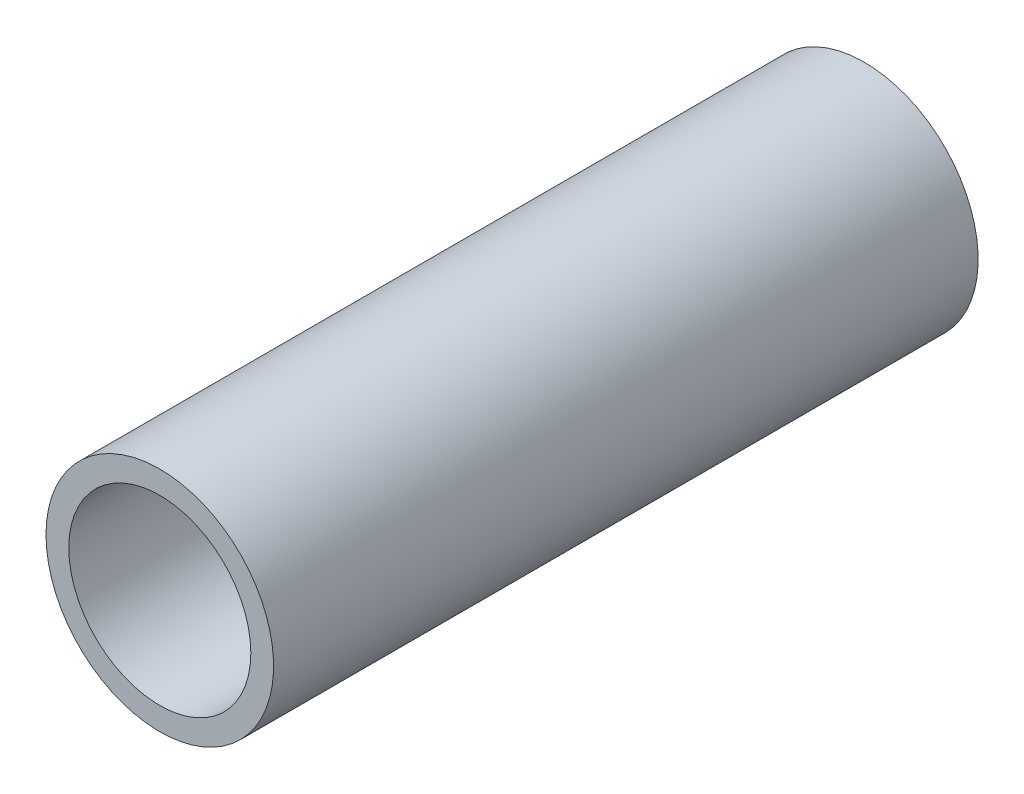
SolidWorks part; units mm, degrees
ref_plane "Front Plane" through (0, 0, 0) normal (0, 0, 1) x (1, 0, 0)
ref_plane "Top Plane" through (0, 0, 0) normal (0, 1, 0) x (1, 0, 0)
ref_plane "Right Plane" through (0, 0, 0) normal (1, 0, 0) x (0, 0, -1)
sketch "Sketch1" plane through (0, 0, 0) normal (0, 0, 1) x (1, 0, 0)
  circle A0 centre (0, 0) radius 1.25
  circle A1 centre (0, 0) radius 1
extrude "Boss-Extrude1" add sketch "Sketch1" along normal blind 7.74
